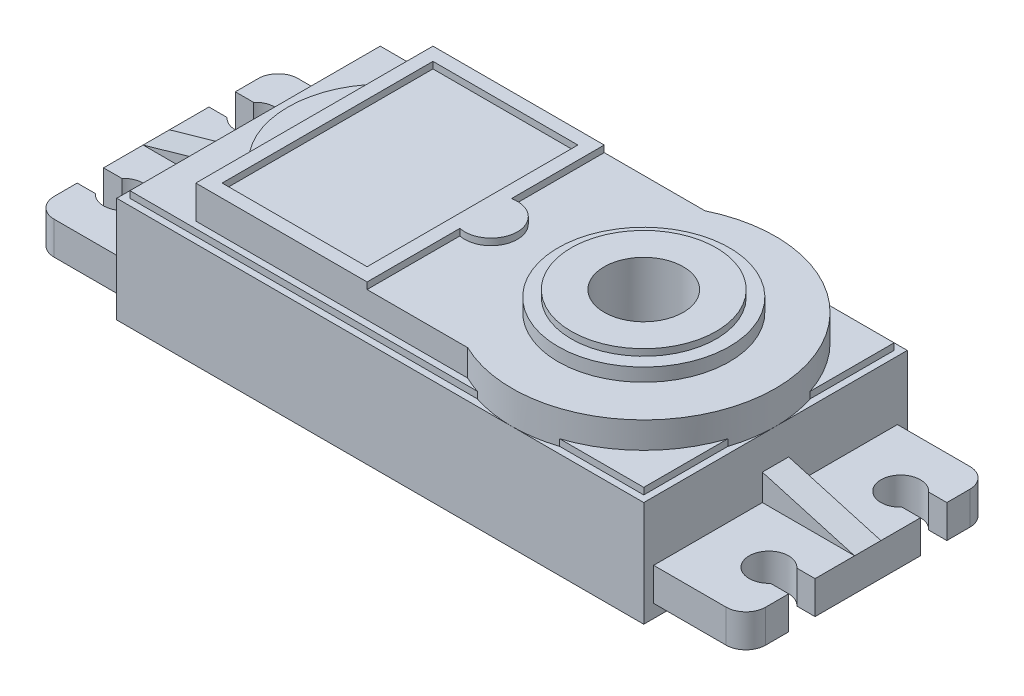
SolidWorks part; units mm, degrees
ref_plane "Piano frontale" through (0, 0, 0) normal (0, 0, 1) x (1, 0, 0)
ref_plane "Piano superiore" through (0, 0, 0) normal (0, 1, 0) x (1, 0, 0)
ref_plane "Piano destro" through (0, 0, 0) normal (1, 0, 0) x (0, 0, -1)
sketch "Schizzo1" plane through (0, 0, 0) normal (0, 1, 0) x (1, 0, 0)
  line L1 (20, -10) -> (-20, -10)
  line L2 (20, -10) -> (20, 10)
  line L3 (20, 10) -> (-20, 10)
  line L4 (-20, -10) -> (-20, 10)
  line L5 (20, -10) -> (-20, 10) construction
  line L6 (20, 10) -> (-20, -10) construction
  point P0 (0, 0)
  dimension "D1" = 20
  dimension "D2" = 40
extrude "Estrusione-Estrusione2" add sketch "Schizzo1" along normal blind 8
sketch "Schizzo2" plane through (0, 0, 0) normal (0, 1, 0) x (1, 0, 0)
  line L0 (-20, 10) -> (-20, -10) construction
  line L1 (16, -8) -> (-16, -8)
  line L2 (18, -6) -> (18, 6)
  line L3 (16, 8) -> (-16, 8)
  line L4 (-18, -6) -> (-18, 6)
  line L5 (16, -7.1111) -> (-16, 7.1111) construction
  line L6 (16, 7.1111) -> (-16, -7.1111) construction
  line L7 (20, 10) -> (-20, 10) construction
  line L8 (-16, 8) -> (-16, 6)
  line L9 (-16, 6) -> (-18, 6)
  line L10 (-18, -6) -> (-16, -6)
  line L11 (-16, -6) -> (-16, -8)
  line L12 (16, 8) -> (16, 6)
  line L13 (16, 6) -> (18, 6)
  line L14 (18, -6) -> (16, -6)
  line L15 (16, -6) -> (16, -8)
  point P0 (0, 0)
  dimension "D1" = 2
  dimension "D2" = 2
  dimension "D3" = 2
extrude "Taglio-Estrusione4" cut sketch "Schizzo2" along normal blind 6
hole_wizard "Foro per Vite M1-1" positions "Schizzo3D1" profile "Schizzo3" hole size "M1" standard "KS"
sketch3d "Schizzo3D1"
  line L0 (-20, 0, -10) -> (-20, 0, 10) construction
  line L1 (-20, 0, 10) -> (20, 0, 10) construction
  point P0 (-18, 0, 8)
  dimension "D1" = 2
  dimension "D2" = 2
sketch "Schizzo3" plane through (-18, 0, 8) normal (1, 0, 0) x (0, 0, -1)
  line L0 (0, 0) -> (0, 5.3906)
  line L1 (0, 5.3906) -> (0.65, 5)
  line L2 (0.65, 5) -> (0.65, 0.025)
  line L3 (0.65, 0.025) -> (0.675, 0)
  line L5 (0.675, 0) -> (0, 0)
  line L6 (-0.65, 0.025) -> (-0.675, 0) construction
  line L10 (0, 5.3906) -> (-0.65, 5) construction
  line L11 (0, -6.35) -> (0, 107.95) construction
  dimension "Hole Dia." = 1.3
  dimension "Hole Depth" = 5
  dimension "Near C'Sink Dia." = 1.35
  dimension "Near C'Sink Angle" = 90
  dimension "Drill Angle" = 118
mirror "Specchia1" about plane through (0, 0, 0) normal (1, 0, 0) of "Foro per Vite M1-1"
mirror "Specchia2" about plane through (0, 0, 0) normal (0, 0, 1) of "Specchia1"
sketch "Schizzo5" plane through (0, 0, 0) normal (0, -1, 0) x (1, 0, 0)
  line L0 (-20, -10) -> (-20, 10) construction
  line L1 (19, -9) -> (-19, -9)
  line L2 (19, -9) -> (19, 9)
  line L3 (19, 9) -> (-19, 9)
  line L4 (-19, -9) -> (-19, 9)
  line L5 (19, -9) -> (-19, 9) construction
  line L6 (19, 9) -> (-19, -9) construction
  line L7 (-20, 10) -> (20, 10) construction
  point P0 (0, 0)
  dimension "D1" = 1
  dimension "D2" = 1
sketch "Schizzo4" plane through (0, 0, 0) normal (0, 0, 1) x (1, 0, 0)
  line L0 (19, 0) -> (-19, 0) construction
  line L1 (19, 0) -> (-19, 0) construction
  line L2 (-20, 8) -> (-20, 0) construction
  line L3 (-19.25, 0) -> (-18.75, 0)
  arc A0 (-18.75, 0) -> (-19.25, 0) centre (-19, 0) ccw
  dimension "D1" = 0.5
  dimension "D2" = 1
sweep "Taglia-Sweep3" cut profiles "Schizzo4" path "Schizzo5"
sketch "Schizzo6" plane through (0, 8, 0) normal (0, 1, 0) x (1, 0, 0)
  line L0 (-20, 10) -> (-20, -10) construction
  line L1 (-15, 9) -> (5.6411, 9)
  line L2 (-15, 9) -> (-15, 5)
  line L3 (-15, -9) -> (11.8461, -9)
  line L5 (-15, 9) -> (11.8461, -9) construction
  line L6 (-15, -9) -> (11.8461, 9) construction
  line L7 (-20, -10) -> (20, -10) construction
  line L8 (20, 10) -> (-20, 10) construction
  line L9 (20, -10) -> (20, 10) construction
  line L10 (-15, -5) -> (-15, -9)
  arc A0 (5.6411, -9) -> (5.6411, 9) centre (10, 0) ccw
  arc A1 (-15, -5) -> (-15, 5) centre (-9.75, 0) cw
  point P0 (-1.5769, 0)
  point P19 (-17, 0)
  dimension "D1" = 5
  dimension "D2" = 1
  dimension "D3" = 1
  dimension "D4" = 10
  dimension "D5" = 2
extrude "Estrusione-Estrusione4" add sketch "Schizzo6" along normal blind 2.5 contours A1 L10 L3 A0 L1 L2 region at (1.5065, 8, 0)
sketch "Schizzo7" plane through (0, 8, 0) normal (0, 1, 0) x (1, 0, 0)
  line L0 (20, 10) -> (10, 10) construction
  line L1 (-19.5, -9.5) -> (19.5, -9.5)
  line L2 (-19.5, -9.5) -> (-19.5, 9.5)
  line L3 (-19.5, 9.5) -> (19.5, 9.5)
  line L4 (19.5, -9.5) -> (19.5, 9.5)
  line L5 (-19.5, -9.5) -> (19.5, 9.5) construction
  line L6 (-19.5, 9.5) -> (19.5, -9.5) construction
  line L7 (-20, 10) -> (-20, -10) construction
  point P0 (0, 0)
  dimension "D1" = 0.5
  dimension "D2" = 0.5
extrude "Estrusione-Estrusione3" add sketch "Schizzo7" along normal blind 0.5
sketch "Schizzo8" plane through (0, 10.5, 0) normal (0, 1, 0) x (1, 0, 0)
  line L0 (-15, -9) -> (5.6411, -9) construction
  line L1 (-15, 9) -> (-2, 9)
  line L2 (-15, 9) -> (-15, -9)
  line L3 (-15, -9) -> (-2, -9)
  line L4 (-2, 9) -> (-2, 1.9577)
  line L5 (-20, 10) -> (-20, -10) construction
  line L6 (-14, -8) -> (-3, -8)
  line L7 (-14, -8) -> (-14, 8)
  line L8 (-14, 8) -> (-3, 8)
  line L9 (-3, -8) -> (-3, 8)
  line L10 (-14, -8) -> (-3, 8) construction
  line L11 (-14, 8) -> (-3, -8) construction
  line L12 (-2, -1.9577) -> (-2, -9)
  arc A0 (-2, -1.9577) -> (-2, 1.9577) centre (-1.5909, 0) ccw
  point P7 (-8.5, 0)
  dimension "D6" = 4
  dimension "D7" = 18.4091
  dimension "D1" = 1
  dimension "D2" = 1
  dimension "D3" = 1
  dimension "D4" = 1
  dimension "D5" = 13
extrude "Estrusione-Estrusione5" add sketch "Schizzo8" along normal blind 0.5
sketch "Schizzo9" plane through (0, 10.5, 0) normal (0, 1, 0) x (1, 0, 0)
  circle A0 centre (10, 0) radius 6.5
  dimension "D1" = 13
extrude "Estrusione-Estrusione6" add sketch "Schizzo9" along normal blind 1
sketch "Schizzo10" plane through (0, 11.5, 0) normal (0, 1, 0) x (1, 0, 0)
  circle A0 centre (10, 0) radius 5.5
  dimension "D1" = 11
extrude "Estrusione-Estrusione7" add sketch "Schizzo10" along normal blind 0.5
sketch "Schizzo11" plane through (0, 12, 0) normal (0, 1, 0) x (1, 0, 0)
  circle A0 centre (10, 0) radius 3
  dimension "D1" = 6
extrude "Taglio-Estrusione5" cut sketch "Schizzo11" against normal through all
ref_plane "Piano1" through (0, 1, 0) normal (0, -1, 0) x (-1, 0, 0)
sketch "Schizzo12" plane through (0, 1, 0) normal (0, -1, 0) x (-1, 0, 0)
  line L0 (-20, -10) -> (-20, 10) construction
  line L2 (-25.5, 9.25) -> (-20, 9.25)
  line L3 (-27, 7.75) -> (-27, -7.75)
  line L4 (-25.5, -9.25) -> (-20, -9.25)
  line L5 (-20, 9.25) -> (-20, -9.25)
  line L6 (-27, 9.25) -> (-20, -9.25) construction
  line L7 (-27, -9.25) -> (-20, 9.25) construction
  arc A0 (-25.5, -9.25) -> (-27, -7.75) centre (-25.5, -7.75) cw
  arc A1 (-27, 7.75) -> (-25.5, 9.25) centre (-25.5, 7.75) cw
  circle A2 centre (-24.5, 5) radius 1.5
  circle A3 centre (-24.5, -5) radius 1.5
  point P0 (-23.5, 0)
  dimension "D3" = 1.5
  dimension "D4" = 3
  dimension "D1" = 18.5
  dimension "D2" = 7
  dimension "D5" = 10
  dimension "D6" = 2.5
  dimension "D7" = 5
extrude "Estrusione-Estrusione8" add sketch "Schizzo12" against normal blind 2.5
sketch "Schizzo13" plane through (0, 3.5, 0) normal (0, 1, 0) x (1, 0, 0)
  line L1 (30.9082, -5.9404) -> (24.8886, -5.9404)
  line L2 (30.9082, -5.9404) -> (30.9082, -4.9899)
  line L3 (30.9082, -4.9899) -> (24.8886, -4.9899)
  line L4 (24.8886, -5.9404) -> (24.8886, -4.9899)
  line L5 (30.9082, -5.9404) -> (24.8886, -4.9899) construction
  line L6 (30.9082, -4.9899) -> (24.8886, -5.9404) construction
  line L7 (34.3221, 4) -> (25.3835, 4)
  line L8 (34.3221, 4) -> (34.3221, 6)
  line L9 (34.3221, 6) -> (25.3835, 6)
  line L10 (25.3835, 4) -> (25.3835, 6)
  line L11 (34.3221, 4) -> (25.3835, 6) construction
  line L12 (34.3221, 6) -> (25.3835, 4) construction
  circle A0 centre (24.5, 5) radius 1.5 construction
  arc A1 (25.618, 4) -> (25.6727, 4.0647) centre (24.5, 5) ccw
  arc A2 (25.6727, 5.9353) -> (25.618, 6) centre (24.5, 5) ccw
  point P0 (27.8984, -5.4652)
  point P5 (29.8528, 5)
  circle M8 centre (24.5, 5) radius 1.5
  line M12 (27, -7.75) -> (27, 7.75)
  dimension "D1" = 2
  dimension "D2" = 8.9386
extrude "Taglio-Estrusione6" cut sketch "Schizzo13" against normal through all contours L8 L9 L7 M12 | L9 L7 M12 M8 region at (26.4345, 3.5, -5) region at (30.661, 3.5, -5)
mirror "Specchia3" about plane through (0, 0, 0) normal (0, 0, 1) of "Taglio-Estrusione6"
mirror "Specchia4" about plane through (0, 0, 0) normal (1, 0, 0) of "Specchia3", "Taglio-Estrusione6", "Estrusione-Estrusione8"
sketch "Schizzo16" plane through (0, 0, 0) normal (0, 0, 1) x (1, 0, 0)
  line L0 (27, 3.5) -> (20, 5.5)
  line L1 (20, 8) -> (20, 0) construction
  line L2 (25.5, 3.5) -> (20, 3.5) construction
  dimension "D1" = 2
rib "Nervatura1" sketch "Schizzo16" sketch "Schizzo16" thickness 2 extrusion direction parallel to sketch draft on no parameters "D1"=2
mirror "Specchia5" about plane through (0, 0, 0) normal (1, 0, 0) of "Nervatura1"
